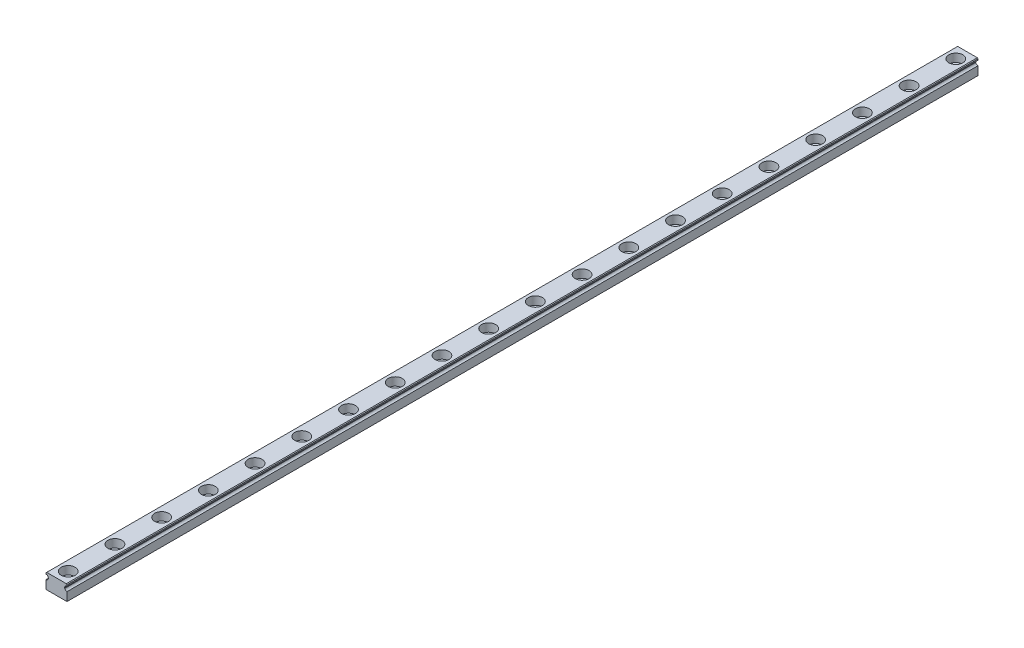
SolidWorks part; units mm, degrees
ref_plane "Спереди" through (0, 0, 0) normal (0, 0, 1) x (1, 0, 0)
ref_plane "Сверху" through (0, 0, 0) normal (0, 1, 0) x (1, 0, 0)
ref_plane "Справа" through (0, 0, 0) normal (1, 0, 0) x (0, 0, -1)
sketch "Sketch1" plane through (0, 0, 0) normal (0, 0, 1) x (1, 0, 0)
  line L0 (0, 0) -> (0, 5.7299) construction
  line L1 (-4.5, -3.25) -> (4.5, -3.25)
  line L2 (-4.5, -3.25) -> (-4.5, 0.45)
  line L3 (-4.5, 3.25) -> (4.5, 3.25)
  line L4 (4.5, -3.25) -> (4.5, 0.45)
  line L5 (-4.5, -3.25) -> (4.5, 3.25) construction
  line L6 (-4.5, 3.25) -> (4.5, -3.25) construction
  line L7 (-4.5, 2.45) -> (-4.5, 3.25)
  line L8 (-3.5318, 1.2) -> (-3.4, 1.2)
  line L9 (3.5318, 1.2) -> (3.4, 1.2)
  line L10 (-3.5318, 1.7) -> (-3.4, 1.7)
  line L11 (-3.4, 1.2) -> (-3.4, 1.7)
  line L12 (3.4, 1.2) -> (3.4, 1.7)
  line L13 (3.5318, 1.7) -> (3.4, 1.7)
  line L14 (4.5, 2.45) -> (4.5, 3.25)
  line L15 (-3.4, 1.45) -> (-4.5, 1.45) construction
  arc A0 (-3.5318, 1.7) -> (-4.5, 2.45) centre (-4.5, 1.45) ccw
  arc A1 (-4.5, 0.45) -> (-3.5318, 1.2) centre (-4.5, 1.45) ccw
  arc A2 (4.5, 0.45) -> (3.5318, 1.2) centre (4.5, 1.45) cw
  arc A3 (3.5318, 1.7) -> (4.5, 2.45) centre (4.5, 1.45) cw
  point P0 (0, 0)
  dimension "D3" = 1
  dimension "D1" = 9
  dimension "D2" = 6.5
  dimension "D4" = 2.05
  dimension "D5" = 6.8
  dimension "D6" = 0.5
extrude "Extrude1" add sketch "Sketch1" along normal blind 390
sketch "Sketch2" plane through (0, 3.25, 0) normal (0, 1, 0) x (1, 0, 0)
  line L0 (4.5, 0) -> (-4.5, 0) construction
  circle A0 centre (0, -5) radius 1.75
  circle A1 centre (0, -5) radius 3
  dimension "D1" = 3.5
  dimension "D2" = 6
  dimension "D3" = 5
extrude "Extrude2" cut sketch "Sketch2" against normal blind 3.5 contours A1
extrude "Extrude3" cut sketch "Sketch" against normal through all contours A0
sketch "Sketch" plane through (0, 3.25, 0) normal (0, 1, 0) x (1, 0, 0) same geometry as "Sketch2"
pattern_linear "LPattern1" count 40 spacing 20 along (0, 0, 1) of "Extrude2", "Extrude3"
chamfer "Chamfer1" distance 0.3 angle 45 2 edges at (4.5, 3.25, 195) (-4.5, 3.25, 195)
